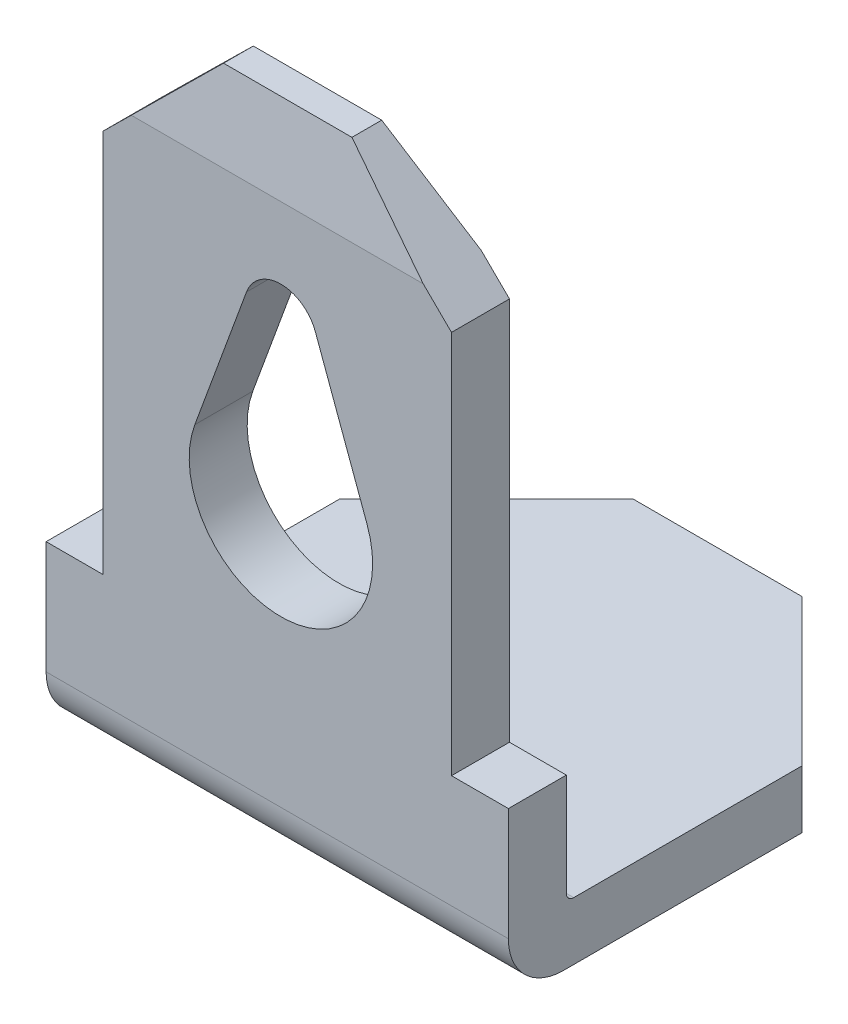
SolidWorks part; units mm, degrees
ref_plane "Front Plane" through (0, 0, 0) normal (0, 0, 1) x (1, 0, 0)
ref_plane "Top Plane" through (0, 0, 0) normal (0, 1, 0) x (1, 0, 0)
ref_plane "Right Plane" through (0, 0, 0) normal (1, 0, 0) x (0, 0, -1)
sketch "Sketch1" plane through (0, 0, 0) normal (1, 0, 0) x (0, 0, -1)
  line L0 (0, 0.1) -> (0, 7.11)
  line L1 (0, 7.11) -> (-0.2414, 8.21)
  line L2 (-0.2414, 8.21) -> (-0.6471, 8.21)
  line L3 (-0.6471, 8.21) -> (-0.79, 7.11)
  line L4 (-0.79, 7.11) -> (-0.79, -0.04)
  line L5 (-0.04, -0.79) -> (5.21, -0.79)
  line L6 (5.21, -0.79) -> (5.21, 0)
  line L7 (5.21, 0) -> (0.1, 0)
  arc A0 (-0.79, -0.04) -> (-0.04, -0.79) centre (-0.04, -0.04) ccw
  arc A1 (0, 0.1) -> (0.1, 0) centre (0.1, 0.1) ccw
  point P3 (5.21, -0.395)
  point P14 (0, 0)
  dimension "D6" = 0.75
  dimension "D7" = 0.1
  dimension "D1" = 9
  dimension "D2" = 0.79
  dimension "D3" = 1.1
  dimension "D5" = 0.79
  dimension "D4" = 6
  dimension "D8" = 0.2414
  dimension "D9" = 0.6471
extrude "Boss-Extrude1" add sketch "Sketch1" along normal blind 6.3
chamfer "Chamfer3" distance 2 angle 45 2 edges at (6.3, -0.395, -5.21) (0, -0.395, -5.21)
sketch "Sketch6" plane through (0, 0, 0) normal (0, 0, -1) x (-1, 0, 0)
  line L0 (-6.3, 0.1) -> (-6.3, 7.11) construction
  line L5 (-6.3, 1.4967) -> (-5.525, 1.4967)
  line L6 (-6.3, 1.4967) -> (-6.3, 8.21)
  line L7 (-6.3, 8.21) -> (-5.525, 8.21)
  line L8 (-5.525, 1.4967) -> (-5.525, 8.21)
  line L9 (-6.3, 8.21) -> (0, 8.21) construction
  line L10 (0, 0.1) -> (0, 7.11) construction
  line L11 (0, 1.4967) -> (-0.775, 1.4967)
  line L12 (0, 1.4967) -> (0, 8.21)
  line L13 (0, 8.21) -> (-0.775, 8.21)
  line L14 (-0.775, 1.4967) -> (-0.775, 8.21)
  line L16 (-6.3, -0.79) -> (0, -0.79) construction
  dimension "D1" = 4.75
  dimension "D2" = 0.775
  dimension "D3" = 6.3
sketch "Sketch5" plane through (0, 0, 0.79) normal (0, 0, 1) x (1, 0, 0)
  line L0 (6.3, 8.21) -> (0, 8.21) construction
  line L1 (2.7306, 5.8088) -> (2.0266, 3.8907)
  line L2 (3.6696, 5.8081) -> (4.3734, 3.8907)
  line L3 (0, 7.11) -> (0, -0.04) construction
  arc A0 (2.0266, 3.8907) -> (4.3734, 3.8907) centre (3.2, 3.46) ccw
  arc A1 (3.6696, 5.8081) -> (2.7306, 5.8088) centre (3.2, 5.6365) ccw
  dimension "D1" = 2.5
  dimension "D3" = 1
  dimension "D2" = 4.75
  dimension "D4" = 2.1765
  dimension "D5" = 2.0266
  dimension "D6" = 2.7306
  dimension "D7" = 3.6696
extrude "Cut-Extrude2" cut sketch "Sketch5" against normal up to surface (0.79 mm away) up to face at (3.15, 3.605, 0)
extrude "Cut-Extrude4" cut sketch "Sketch6" against normal up to surface (0.79 mm away) up to face at (3.2001, 4.5114, 0.79)
sketch "Sketch4" plane through (0, 0, 0) normal (0, 0, 1) x (1, 0, 0)
  line L3 (7.2834, 6.71) -> (-2.6937, 6.71) construction
  line L10 (5.525, 8.21) -> (0.775, 8.21) construction
  line L17 (3.15, 8.21) -> (3.15, -1.2073) construction
  line L18 (2.275, 8.21) -> (0.775, 8.21)
  line L19 (0.7555, 6.71) -> (2.275, 8.21)
  line L20 (0.775, 8.21) -> (0.7555, 6.71)
  line L21 (5.5445, 6.71) -> (4.025, 8.21)
  line L22 (5.525, 8.21) -> (5.5445, 6.71)
  line L23 (4.025, 8.21) -> (5.525, 8.21)
  dimension "D4" = 1.5
extrude "Cut-Extrude6" cut sketch "Sketch4" against normal through all both and the other way through all
equation "\"D5@Sketch1\"=\"D2@Sketch1\""
equation "\"D2@Sketch6\"=(\"D3@Sketch6\"-\"D1@Sketch6\")/2"
